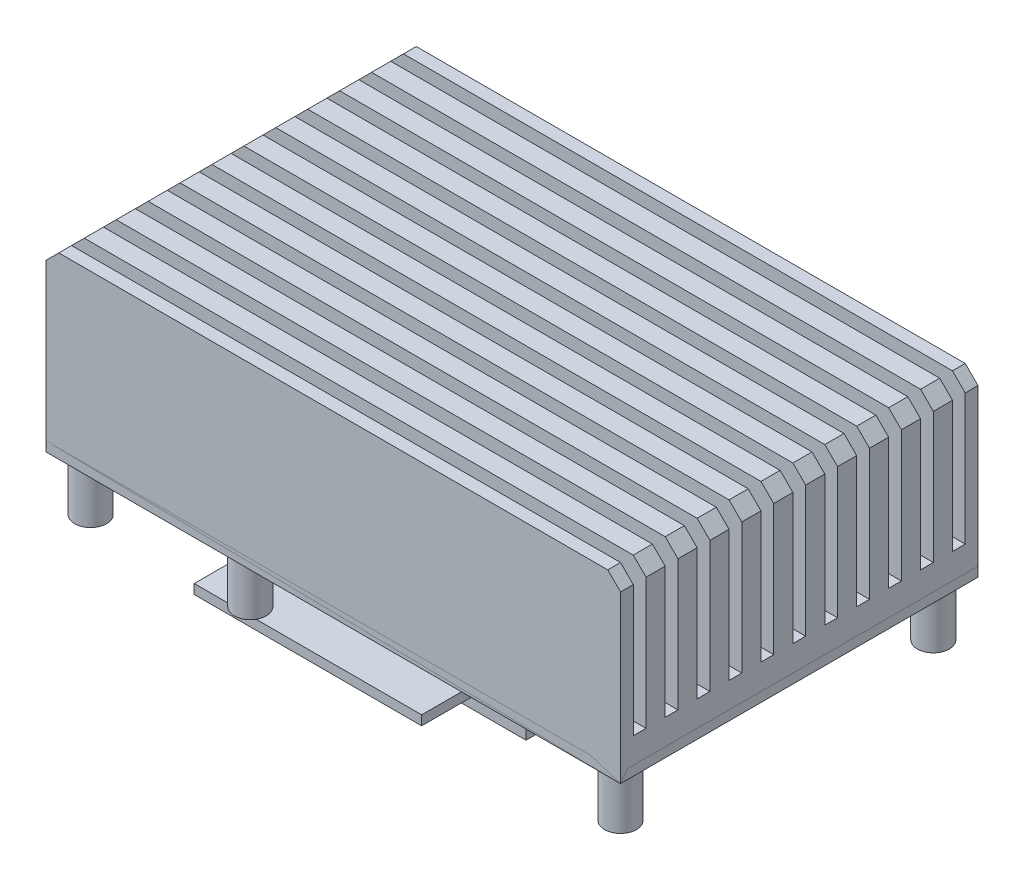
SolidWorks part; units mm, degrees
ref_plane "Front Plane" through (0, 0, 0) normal (0, 0, 1) x (1, 0, 0)
ref_plane "Top Plane" through (0, 0, 0) normal (0, 1, 0) x (1, 0, 0)
ref_plane "Right Plane" through (0, 0, 0) normal (1, 0, 0) x (0, 0, -1)
sketch "Sketch1" plane through (0, 0, 0) normal (0, 1, 0) x (1, 0, 0)
  line L1 (-45, 28) -> (45, 28)
  line L2 (-45, 28) -> (-45, -28)
  line L3 (-45, -28) -> (45, -28)
  line L4 (45, 28) -> (45, -28)
  line L5 (-45, 28) -> (45, -28) construction
  line L6 (-45, -28) -> (45, 28) construction
  point P0 (0, 0)
  dimension "D1" = 90
  dimension "D2" = 56
extrude "Boss-Extrude1" add sketch "Sketch1" along normal blind 1.5
sketch "Sketch2" plane through (0, 0, 0) normal (0, 1, 0) x (1, 0, 0)
  line L1 (-45, 28) -> (45, 28)
  line L2 (-45, 28) -> (-45, -28)
  line L3 (-45, -28) -> (45, -28)
  line L4 (45, 28) -> (45, -28)
extrude "Boss-Extrude2" add sketch "Sketch2" along normal blind 28 separate body
chamfer "Chamfer1" distance 2 angle 45 2 edges at (-45, 28, 0) (45, 28, 0)
sketch "Sketch3" plane through (0, 0, 0) normal (1, 0, 0) x (0, 0, -1)
  line L0 (-28, 28) -> (28, 28) construction
  line L1 (-26, 28) -> (-24, 28)
  line L2 (-26, 28) -> (-26, 5.4964)
  line L3 (-26, 5.4964) -> (-24, 5.4964)
  line L4 (-24, 28) -> (-24, 5.4964)
  line L5 (-28, 26) -> (-28, 0) construction
  dimension "D1" = 2
  dimension "D2" = 2
extrude "Cut-Extrude1" cut sketch "Sketch3" against normal through all both and the other way through all
pattern_linear "LPattern1" count 11 spacing 5 along (0, 0, -1) of "Cut-Extrude1"
sketch "Sketch4" plane through (0, 0, 0) normal (0, -1, 0) x (1, 0, 0)
  line L0 (-41.5, 24.5) -> (41.5, 24.5) construction
  line L1 (-41.5, 24.5) -> (-41.5, -24.5) construction
  line L2 (-41.5, 0) -> (-45, 0) construction
  line L3 (-45, -28) -> (-45, 28) construction
  line L4 (0, 24.5) -> (0, 28) construction
  line L5 (-45, 28) -> (45, 28) construction
  circle A0 centre (-41.5, 24.5) radius 1.5
  circle A1 centre (-41.5, 24.5) radius 2.5
  circle A2 centre (-16.5, 24.5) radius 1.5
  circle A3 centre (-16.5, 24.5) radius 2.5
  circle A4 centre (41.5, 24.5) radius 1.5
  circle A5 centre (41.5, 24.5) radius 2.5
  circle A6 centre (-41.5, -24.5) radius 2.5
  circle A7 centre (-41.5, -24.5) radius 1.5
  circle A8 centre (-16.5, -24.5) radius 1.5
  circle A9 centre (-16.5, -24.5) radius 2.5
  circle A10 centre (41.5, -24.5) radius 1.5
  circle A11 centre (41.5, -24.5) radius 2.5
  point P26 (0, 28)
  dimension "D1" = 3
  dimension "D2" = 1
  dimension "D3" = 25
  dimension "D4" = 58
  dimension "D5" = 49
extrude "Boss-Extrude3" add sketch "Sketch4" along normal blind 8.5 separate body
sketch "Sketch5" plane through (0, 0, 0) normal (0, 0, 1) x (1, 0, 0)
  line L1 (0, 8.5) -> (-14.5, 8.5)
  line L2 (0, 8.5) -> (0, 1.5)
  line L3 (0, 1.5) -> (-14.5, 1.5)
  line L4 (-14.5, 8.5) -> (-14.5, 1.5)
  line L5 (20.8, 8.1) -> (2.8, 8.1)
  line L6 (20.8, 8.1) -> (20.8, 1.5)
  line L7 (20.8, 1.5) -> (2.8, 1.5)
  line L8 (2.8, 8.1) -> (2.8, 1.5)
  line L9 (-45, 1.5) -> (45, 1.5) construction
  line L10 (45, 1.5) -> (45, 0) construction
  dimension "D1" = 14.5
  dimension "D2" = 7
  dimension "D3" = 18
  dimension "D4" = 6.6
  dimension "D5" = 24.2
  dimension "D6" = 45
sketch "Sketch6" plane through (0, 0, 0) normal (0, 1, 0) x (1, 0, 0)
  line L1 (-24.0358, -25.744) -> (11.5884, -25.744)
  line L2 (-24.0358, -25.744) -> (-24.0358, -2.0672)
  line L3 (-24.0358, -2.0672) -> (11.5884, -2.0672)
  line L4 (11.5884, -25.744) -> (11.5884, -2.0672)
extrude "Boss-Extrude4" add sketch "Sketch6" against normal blind 1.5 from offset 8.5 separate body offset against normal yes
sketch "Sketch7" plane through (0, -10, 0) normal (0, -1, 0) x (1, 0, 0)
  line L0 (11.5884, 2.0672) -> (-24.0358, 2.0672) construction
  line L1 (-22.2481, 7.5177) -> (9.7134, 7.5177)
  line L2 (-22.2481, 7.5177) -> (-22.2481, 2.0672)
  line L3 (-22.2481, 2.0672) -> (9.7134, 2.0672)
  line L4 (9.7134, 7.5177) -> (9.7134, 2.0672)
extrude "Boss-Extrude5" add sketch "Sketch7" along normal offset from surface (12 mm away) 50 separate body up to face at (0, 28, 27)
extrude "Boss-Extrude6" add sketch "Sketch5" against normal offset from surface (29 mm away) 1 separate body up to face at (0, 18, -28) offset beyond the face yes
